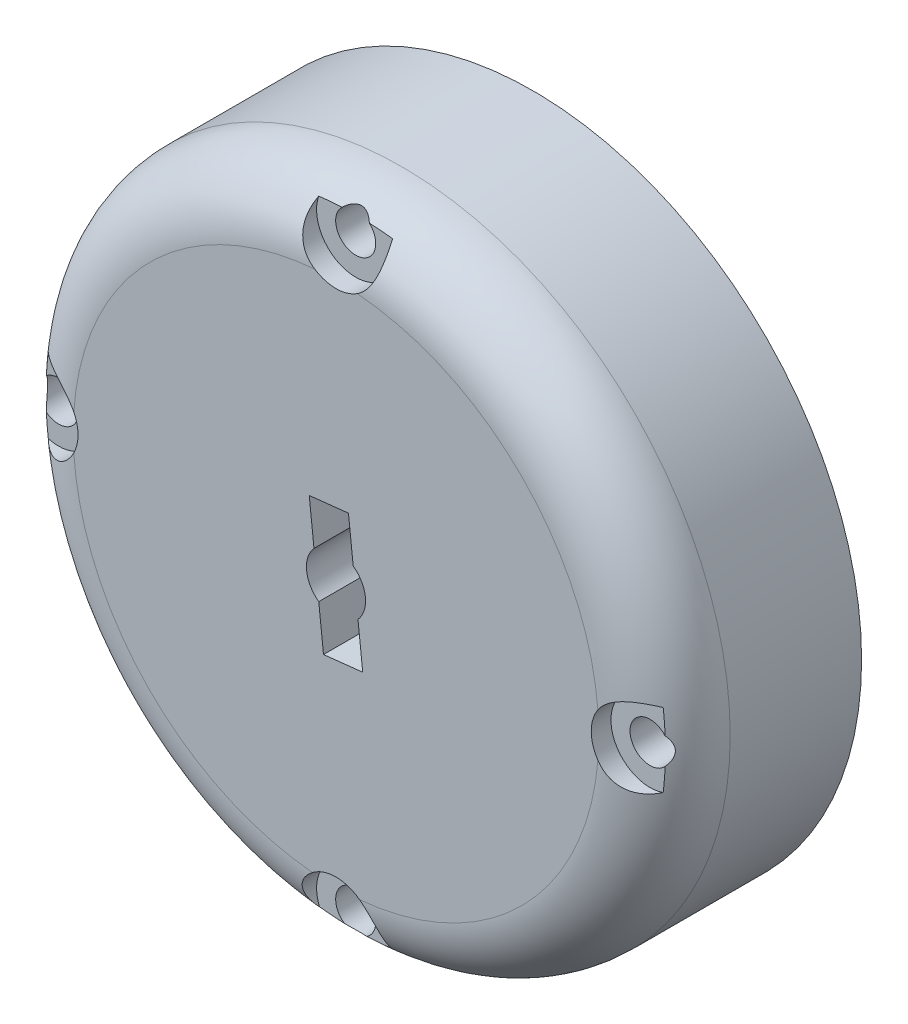
SolidWorks part; units mm, degrees
ref_plane "Front Plane" through (0, 0, 0) normal (0, 0, 1) x (1, 0, 0)
ref_plane "Top Plane" through (0, 0, 0) normal (0, 1, 0) x (1, 0, 0)
ref_plane "Right Plane" through (0, 0, 0) normal (1, 0, 0) x (0, 0, -1)
sketch "Sketch1" plane through (0, 0, 0) normal (0, 0, 1) x (1, 0, 0)
  circle A0 centre (0, 0) radius 19
  circle A1 centre (0, 0) radius 25
  dimension "D1" = 50
  dimension "D2" = 38
extrude "Boss-Extrude1" add sketch "Sketch1" along normal blind 5
sketch "Sketch2" plane through (0, 0, 5) normal (0, 0, 1) x (1, 0, 0)
  circle A0 centre (0, 0) radius 25 construction
  circle A1 centre (0, 0) radius 25
extrude "Boss-Extrude2" add sketch "Sketch2" along normal blind 10
fillet "Fillet1" radius 5 2 edges at (19, 0, 5) (25, 0, 15)
hole_wizard "CBORE for #3 Binding Head Machine Screw1" positions "Sketch13" profile "Sketch14" counterbore size "#3" standard "ANSI Inch" end condition through all
sketch "Sketch13" plane through (0, 0, 15) normal (0, 0, 1) x (1, 0, 0)
  point P0 (0, 22.4351)
  point P2 (0, -22.2959)
  point P4 (22.4003, 0)
  point P6 (-22.609, 0)
sketch "Sketch14" plane through (0, 22.4351, 15) normal (1, 0, 0) x (0, -1, 0)
  line L0 (0, 0) -> (0, 15)
  line L1 (0, 15) -> (1.524, 15)
  line L3 (1.524, 15) -> (1.524, 1.4986)
  line L4 (1.524, 1.4986) -> (2.9769, 1.4986)
  line L5 (2.9769, 1.4986) -> (2.9769, 0)
  line L7 (2.9769, 0) -> (0, 0)
  line L11 (0, -6.35) -> (0, 107.95) construction
  dimension "Thru Hole Dia." = 3.048
  dimension "Thru Hole Depth" = 15
  dimension "C'Bore Dia." = 5.9538
  dimension "C'Bore Depth" = 1.4986
sketch "Sketch15" plane through (0, 0, 5) normal (0, 0, -1) x (-1, 0, 0)
  line L6 (1.6762, 1.5009) -> (2.0371, 4.8073)
  line L7 (2.0371, 4.8073) -> (-0.9486, 5.1332)
  line L8 (-0.9486, 5.1332) -> (-1.3092, 1.8299)
  line L9 (-1.6731, -1.5044) -> (-2.0337, -4.8077)
  line L10 (-2.0337, -4.8077) -> (0.9521, -5.1336)
  line L11 (0.9521, -5.1336) -> (1.313, -1.8272)
  line L12 (1.6762, 1.5009) -> (2.0371, 4.8073)
  line L13 (2.0371, 4.8073) -> (-0.9486, 5.1332)
  line L14 (-0.9486, 5.1332) -> (-1.3092, 1.8299)
  line L15 (-1.6731, -1.5044) -> (-2.0337, -4.8077)
  line L16 (-2.0337, -4.8077) -> (0.9521, -5.1336)
  line L17 (0.9521, -5.1336) -> (1.313, -1.8272)
  arc A4 (2.2367, -0.2441) -> (1.6762, 1.5009) centre (0, 0) ccw
  arc A5 (-1.3092, 1.8299) -> (-2.2367, 0.2441) centre (0, 0) ccw
  arc A6 (-2.2367, 0.2441) -> (-1.6731, -1.5044) centre (0, 0) ccw
  arc A7 (1.313, -1.8272) -> (2.2367, -0.2441) centre (0, 0) ccw
  arc A8 (2.2367, -0.2441) -> (1.6762, 1.5009) centre (0, 0) ccw
  arc A9 (-1.3092, 1.8299) -> (-2.2367, 0.2441) centre (0, 0) ccw
  arc A10 (-2.2367, 0.2441) -> (-1.6731, -1.5044) centre (0, 0) ccw
  arc A11 (1.313, -1.8272) -> (2.2367, -0.2441) centre (0, 0) ccw
  dimension "D1" = 0
extrude "Cut-Extrude1" cut sketch "Sketch15" against normal blind 10 from offset 3
